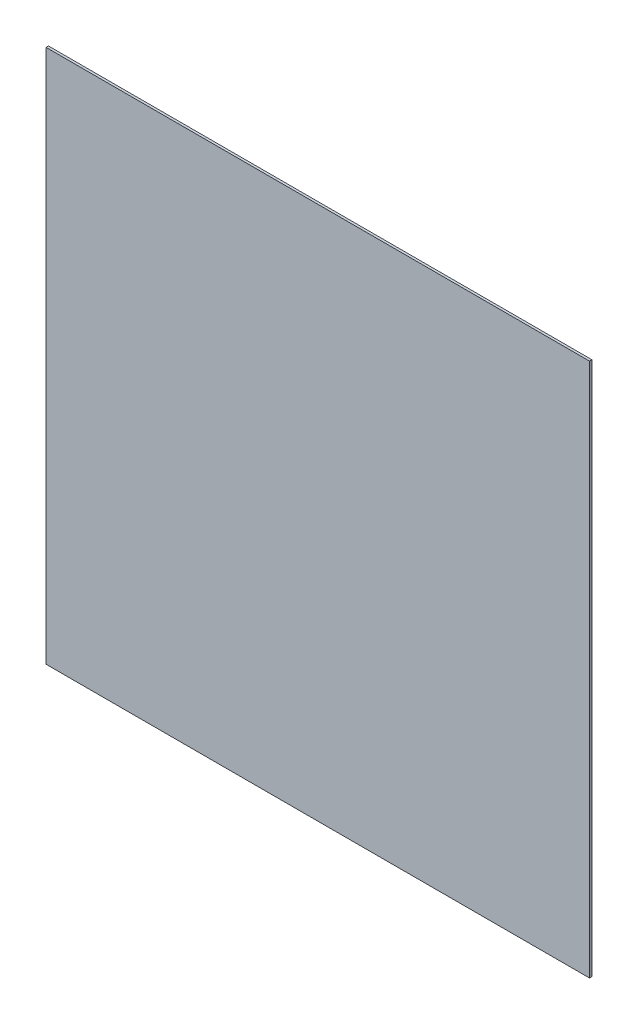
SolidWorks part; units mm, degrees
material "Mahogany"
ref_plane "Front Plane" through (0, 0, 0) normal (0, 0, 1) x (1, 0, 0)
ref_plane "Top Plane" through (0, 0, 0) normal (0, 1, 0) x (1, 0, 0)
ref_plane "Right Plane" through (0, 0, 0) normal (1, 0, 0) x (0, 0, -1)
sketch "Sketch1" plane through (0, 0, 0) normal (0, 0, 1) x (1, 0, 0)
  line L1 (-360, -354) -> (360, -354)
  line L2 (-360, -354) -> (-360, 354)
  line L3 (-360, 354) -> (360, 354)
  line L4 (360, -354) -> (360, 354)
  line L5 (-360, -354) -> (360, 354) construction
  line L6 (-360, 354) -> (360, -354) construction
  point P0 (0, 0)
  dimension "D1" = 720
  dimension "D2" = 708
extrude "Boss-Extrude1" add sketch "Sketch1" along normal blind 3.175
equation "\"W\"= 1500"
equation "\"L\"= 780"
equation "\"H\"= 780"
equation "\"ARM_BOLT_SPACING\"= 166"
equation "\"ARM_TO_WALL\"= 200"
equation "\"D1@Sketch1\"=(\"W\"/2)-30"
equation "\"D2@Sketch1\"=\"H\"-72"
